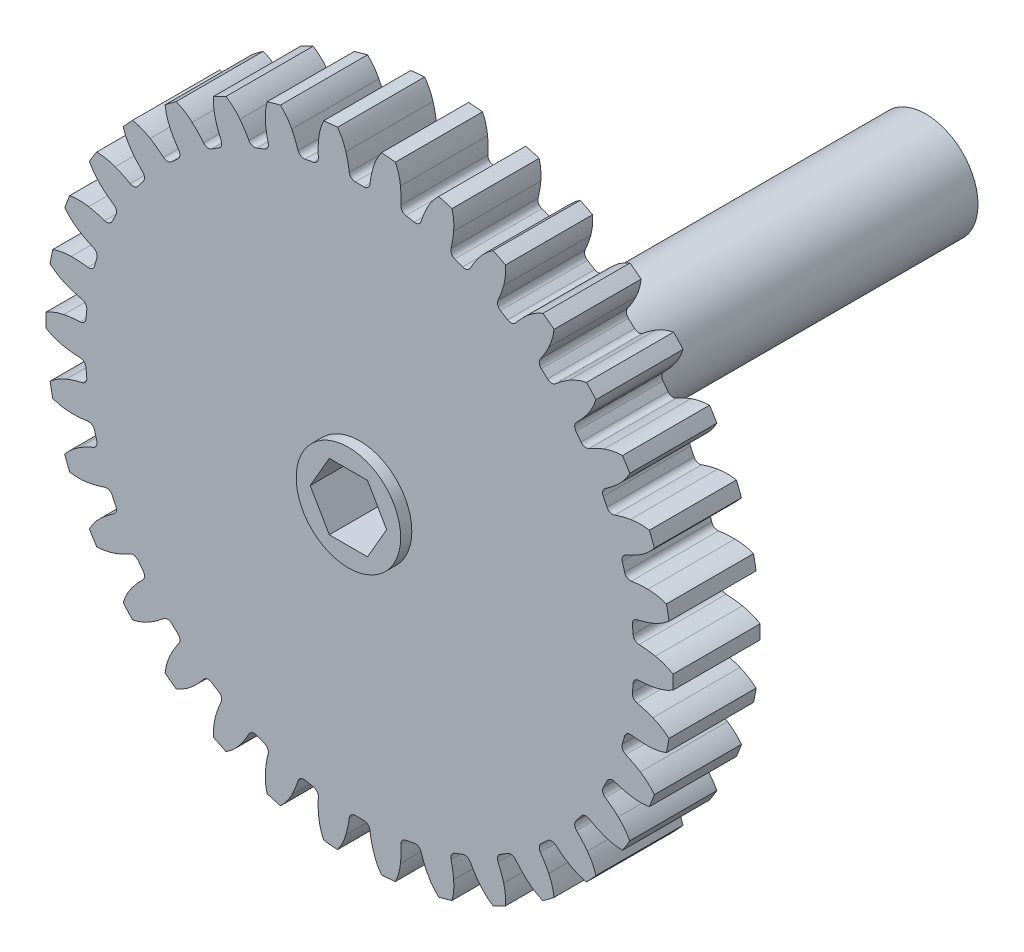
SolidWorks part; units mm, degrees
material "PLA/ABS"
ref_plane "Front" through (0, 0, 0) normal (0, 0, 1) x (1, 0, 0)
ref_plane "Top" through (0, 0, 0) normal (0, 1, 0) x (1, 0, 0)
ref_plane "Right" through (0, 0, 0) normal (1, 0, 0) x (0, 0, -1)
sketch "Sketch1" plane through (0, 0, 0) normal (0, 0, 1) x (1, 0, 0)
  line L0 (0, 0) -> (21.59, 0) construction
  line L1 (21.59, 0) -> (22.86, 0) construction
  circle A0 centre (0, 0) radius 21.59 construction
  circle A1 centre (0, 0) radius 22.86
  dimension "D1" = 43.18
  dimension "D2" = 1.27
extrude "Round Stock" add sketch "Sketch1" along normal mid plane 6.35
sketch "Sketch2" plane through (0, 0, 3.175) normal (0, 0, 1) x (1, 0, 0)
  line L0 (0, 0) -> (20.0025, 0) construction
  line L1 (20.0025, 0) -> (21.59, 0) construction
  line L2 (0, 0) -> (-22.86, 0) construction
  line L3 (0, 0) -> (-22.4708, -4.2005) construction
  line L4 (-22.5584, -3.7009) -> (-21.383, -2.9823) construction
  line L5 (-21.383, -2.9823) -> (-19.8439, -2.5135) construction
  line L6 (-22.8544, -0.5072) -> (-21.5669, -0.9976) construction
  line L7 (-21.5669, -0.9976) -> (-19.9679, -1.1756) construction
  line L8 (-21.1997, -3.9629) -> (-21.383, -2.9823) construction
  line L9 (-21.5669, -0.9976) -> (-21.5669, 0) construction
  line L12 (0, 0) -> (-21.5669, -0.9976) construction
  line L13 (0, 0) -> (-21.383, -2.9823) construction
  line L14 (-21.383, -2.9823) -> (-20.3452, -10.4237) construction
  line L15 (-21.5669, -0.9976) -> (-21.9141, 6.5078) construction
  line L16 (-21.383, -2.9823) -> (-21.5669, -0.9976) construction
  line L17 (-19.9172, -1.8456) -> (-19.9679, -1.1756) construction
  line L18 (-19.9172, -1.8456) -> (-19.8439, -2.5135) construction
  circle A0 centre (0, 0) radius 21.59 construction
  circle A1 centre (0, 0) radius 20.0025 construction
  circle A2 centre (0, 0) radius 22.86 construction
  arc A3 (-22.5584, -3.7009) -> (-22.8544, -0.5072) centre (0, 0) cw
  arc A4 (-19.8439, -2.5135) -> (-19.9679, -1.1756) centre (0, 0) cw construction
  arc A6 (-22.5584, -3.7009) -> (-21.383, -2.9823) centre (-19.9206, -6.695) cw
  arc A7 (-22.8544, -0.5072) -> (-21.5669, -0.9976) centre (-20.8116, 2.9206) ccw
  arc A8 (-21.383, -2.9823) -> (-20.2324, -2.6305) centre (-18.5705, -10.1225) cw
  arc A9 (-21.5669, -0.9976) -> (-20.3713, -1.132) centre (-20.1143, 6.5378) ccw
  arc A10 (-20.2324, -2.6305) -> (-19.8867, -2.1488) centre (-20.3287, -2.1965) ccw
  arc A11 (-20.3713, -1.132) -> (-19.943, -1.542) centre (-20.3862, -1.5763) cw
  arc A12 (-19.8867, -2.1488) -> (-19.943, -1.542) centre (0, 0) cw
  dimension "D6" = 43.18
  dimension "D9" = 0.4445
  dimension "D12" = 3.9903
  dimension "D2" = 1.5875
  dimension "D3" = 10.588
  dimension "D4" = 0.9976
  dimension "D5" = 0.9976
  dimension "D11" = 1.9932
  dimension "D8" = 14.5
  dimension "D7" = 14.5
  dimension "D14" = 9
  dimension "D15" = 9
extrude "Single Tooth" cut sketch "Sketch2" against normal through all
ref_axis "Axis" through (0, 0, 50) along (0, 0, -1)
pattern_circular "Tooth Pattern" count 34 over 360 about axis through (0, 0, 50) along (0, 0, -1) of "Single Tooth"
sketch "Sketch4" plane through (0, 0, 3.175) normal (0, 0, 1) x (1, 0, 0)
  circle A0 centre (0, 0) radius 3.1039
  dimension "D1" = 6.2078
extrude "TopBearingBoss" [suppressed] add sketch "Sketch4" along normal blind 0.635
mirror "BottomBearingBoss" [suppressed] about plane through (0, 0, 0) normal (0, 0, 1)
sketch "Sketch6" [suppressed] plane through (0, 0, 0) normal (0, 0, 1) x (1, 0, 0)
  line L1 (1.4005, 2.4257) -> (-1.4005, 2.4257)
  line L2 (-1.4005, 2.4257) -> (-2.801, 0)
  line L3 (-2.801, 0) -> (-1.4005, -2.4257)
  line L4 (-1.4005, -2.4257) -> (1.4005, -2.4257)
  line L5 (1.4005, -2.4257) -> (2.801, 0)
  line L6 (2.801, 0) -> (1.4005, 2.4257)
  circle A0 centre (0, 0) radius 2.4257 construction
  circle A1 centre (0, 0) radius 2.4257 construction
extrude "Hex" [suppressed] cut sketch "Sketch6" against normal through all both and the other way through all
sketch "Sketch7" plane through (0, 0, -3.175) normal (0, 0, -1) x (-1, 0, 0)
  line L7 (1.3931, -2.413) -> (2.7863, 0)
  line L8 (2.7863, 0) -> (1.3931, 2.413)
  line L9 (1.3931, 2.413) -> (-1.3931, 2.413)
  line L10 (-1.3931, 2.413) -> (-2.7863, 0)
  line L11 (-2.7863, 0) -> (-1.3931, -2.413)
  line L12 (-1.3931, -2.413) -> (1.3931, -2.413)
  circle A1 centre (0, 0) radius 2.413 construction
  dimension "D1" = 4.826
extrude "Cut-Extrude1" cut sketch "Sketch7" against normal through all
sketch "Sketch8" plane through (0, 0, -3.175) normal (0, 0, -1) x (-1, 0, 0)
  line L6 (1.3931, -2.413) -> (2.7863, 0)
  line L7 (-1.3931, -2.413) -> (1.3931, -2.413)
  line L8 (-2.7863, 0) -> (-1.3931, -2.413)
  line L9 (-1.3931, 2.413) -> (-2.7863, 0)
  line L10 (1.3931, 2.413) -> (-1.3931, 2.413)
  line L11 (2.7863, 0) -> (1.3931, 2.413)
  line L12 (1.3931, -2.413) -> (2.7863, 0)
  line L13 (-1.3931, -2.413) -> (1.3931, -2.413)
  line L14 (-2.7863, 0) -> (-1.3931, -2.413)
  line L15 (-1.3931, 2.413) -> (-2.7863, 0)
  line L16 (1.3931, 2.413) -> (-1.3931, 2.413)
  line L17 (2.7863, 0) -> (1.3931, 2.413)
  circle A2 centre (0, 0) radius 3.81
  point P4 (0, 0)
  dimension "D1" = 7.62
  dimension "D2" = 0
extrude "Boss-Extrude1" add sketch "Sketch8" along normal blind 34.925
chamfer "Chamfer1" distance 1.27 angle 45 1 edges at (3.81, 0, -3.175)
sketch "Sketch9" plane through (0, 0, 3.175) normal (0, 0, 1) x (1, 0, 0)
  line L6 (-1.3931, -2.413) -> (1.3931, -2.413)
  line L7 (-2.7863, 0) -> (-1.3931, -2.413)
  line L8 (-1.3931, 2.413) -> (-2.7863, 0)
  line L9 (1.3931, 2.413) -> (-1.3931, 2.413)
  line L10 (2.7863, 0) -> (1.3931, 2.413)
  line L11 (1.3931, -2.413) -> (2.7863, 0)
  line L12 (-1.3931, -2.413) -> (1.3931, -2.413)
  line L13 (-2.7863, 0) -> (-1.3931, -2.413)
  line L14 (-1.3931, 2.413) -> (-2.7863, 0)
  line L15 (1.3931, 2.413) -> (-1.3931, 2.413)
  line L16 (2.7863, 0) -> (1.3931, 2.413)
  line L17 (1.3931, -2.413) -> (2.7863, 0)
  circle A0 centre (0, 0) radius 3.81
  dimension "D2" = 7.62
  dimension "D1" = 0
extrude "Boss-Extrude2" add sketch "Sketch9" along normal blind 0.8128
equation "\"N_teeth\"= \"No_Teeth\""
equation "\"pitch_diameter\"= \"N_teeth\" / \"Pitch\""
equation "\"Pd\"=\"N_teeth\"/\"pitch_diameter\""
equation "\"addendum\"=1.000/\"Pd\""
equation "\"face_width\"=0.25"
equation "\"deddendum\"=1.250/\"Pd\""
equation "\"D3@Sketch2\" = 360/\"N_teeth\""
equation "\"tooth_thickness\"=1.571/\"Pd\""
equation "\"D4@Sketch2\" = \"tooth_thickness\"/2"
equation "\"D5@Sketch2\" = \"tooth_thickness\"/2"
equation "\"Pressure_Angle\"= iif ( \"Pitch\" = 20 , 14.500000 , iif ( \"Pitch\" = 32 , 20 , 20 ) )"
equation "\"base_fillet\"=0.35/\"Pd\""
equation "\"D12@Sketch2\" = 2*\"tooth_thickness\""
equation "\"hub_projection\"=0.250000"
equation "\"sss_diam\"= 0.062500"
equation "\"D1@Sketch1\"=\"pitch_diameter\""
equation "\"D2@Sketch1\"=\"addendum\""
equation "\"D1@Round Stock\" = \"face_width\""
equation "\"D2@Sketch2\"=\"deddendum\""
equation "\"D6@Sketch2\"=\"pitch_diameter\""
equation "\"D7@Sketch2\"=\"Pressure_Angle\""
equation "\"D8@Sketch2\"=\"D7@Sketch2\""
equation "\"D9@Sketch2\"=\"base_fillet\""
equation "\"D1@Tooth Pattern\" = \"N_teeth\""
equation "\"Pitch\"= \"GearPitch\""
equation "\"BossDia\"= \"BoreDia\" * 1.3"
equation "\"Hex\"= iif ( \"HexBore\" = 1 , \"unsuppressed\" , \"suppressed\" )"
equation "\"TopBearingBoss\" = iif ( \"Bearing_Boss\" = 0 , \"suppressed\" , \"unsuppressed\" )"
equation "\"BottomBearingBoss\"= iif ( \"Bearing_Boss\" > 1 , \"unsuppressed\" , \"suppressed\" )"
equation "\"D1@Sketch4\"=\"BossDia\""
equation "\"ToothCount\"= iif ( \"No_Teeth\" < 22 , \"suppressed\" , \"unsuppressed\" )"
